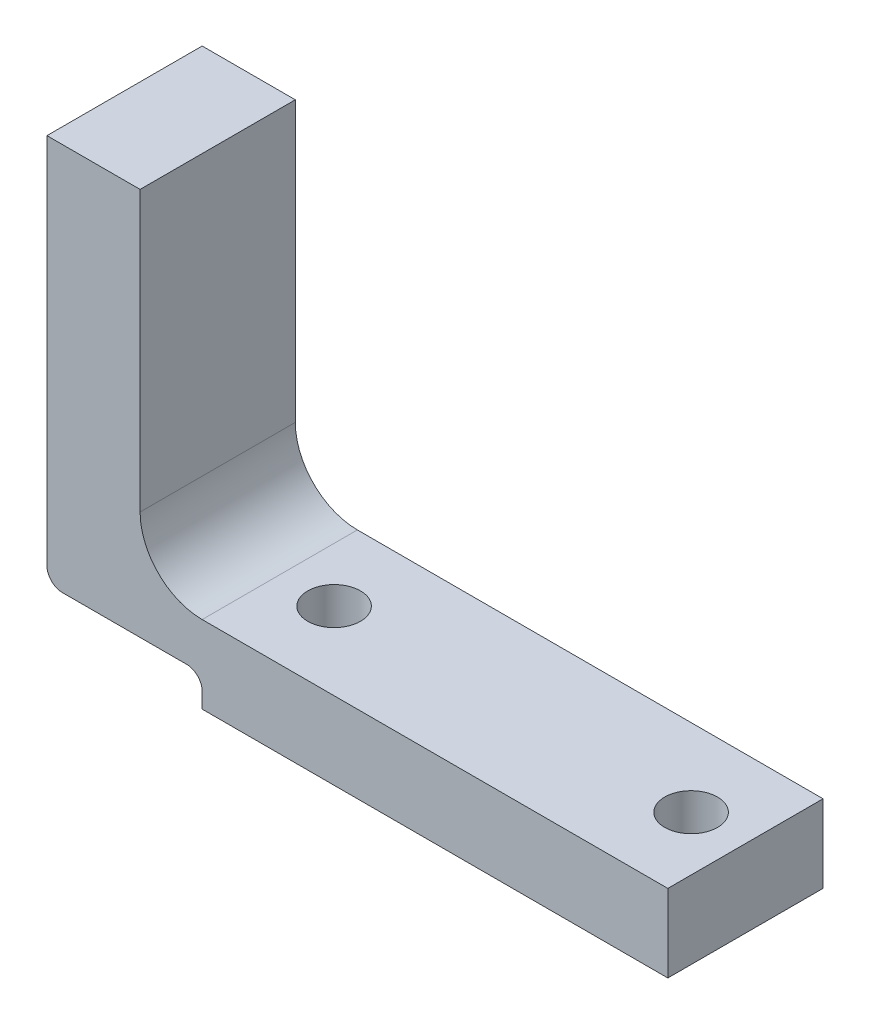
SolidWorks part; units mm, degrees
ref_plane "前视基准面" through (0, 0, 0) normal (0, 0, 1) x (1, 0, 0)
ref_plane "上视基准面" through (0, 0, 0) normal (0, 1, 0) x (1, 0, 0)
ref_plane "右视基准面" through (0, 0, 0) normal (1, 0, 0) x (0, 0, -1)
sketch "草图1" plane through (0, 0, 0) normal (0, 0, 1) x (1, 0, 0)
  line L0 (0, 27) -> (0, 0)
  line L1 (0, 0) -> (40, 0)
  line L2 (40, 0) -> (40, 5)
  line L3 (40, 5) -> (6, 5)
  line L4 (6, 5) -> (6, 27)
  line L5 (6, 27) -> (0, 27)
  dimension "D1" = 34
  dimension "D2" = 27
  dimension "D3" = 6
  dimension "D4" = 5
extrude "凸台-拉伸1" add sketch "草图1" along normal mid plane 10
sketch "草图2" plane through (0, 5, 0) normal (0, 1, 0) x (1, 0, 0)
  line L0 (13.5, 0) -> (36.5, 0)
  dimension "D1" = 23
  dimension "D2" = 3.5
fillet "圆角1" radius 4 1 edges at (6, 5, 0)
hole_wizard "M3 间隙孔1" positions "3D草图1" profile "草图4" hole size "M3" standard "GB" end condition through all
sketch3d "3D草图1"
  point P0 (13.5, 5, 0)
  point P3 (36.5, 5, 0)
sketch "草图4" plane through (13.5, 5, 0) normal (1, 0, 0) x (0, 0, 1)
  line L0 (0, 0) -> (0, 5)
  line L1 (0, 5) -> (1.7, 5)
  line L2 (1.7, 5) -> (1.7, 0)
  line L5 (1.7, 0) -> (0, 0)
  line L11 (0, -6.35) -> (0, 107.95) construction
  dimension "通孔孔直径" = 3.4
  dimension "通孔孔深度" = 5
sketch "草图5" plane through (0, 0, 0) normal (1, 0, 0) x (0, 0, -1)
  line L0 (0, 6) -> (0, 23)
  line L1 (0, 5) -> (0, 27) construction
  line L2 (-5, 27) -> (5, 27) construction
  dimension "D1" = 4
  dimension "D2" = 17
hole_wizard "M3 螺纹孔1" positions "3D草图2" profile "草图6" tap size "M3" standard "GB"
sketch3d "3D草图2"
  point P0 (0, 6, 0)
  point P3 (0, 23, 0)
cosmetic thread "孔螺蚊线1" parameters "D1"=5, "D2"=3
cosmetic thread "孔螺蚊线2" parameters "D1"=5, "D2"=3
sketch "草图6" plane through (0, 6, 0) normal (0, 1, 0) x (0, 0, 1)
  line L0 (0, 0) -> (0, 5.7511)
  line L1 (0, 5.7511) -> (1.25, 5)
  line L2 (1.25, 5) -> (1.25, 0)
  line L5 (1.25, 0) -> (0, 0)
  line L10 (0, 5.7511) -> (-1.25, 5) construction
  line L11 (0, -6.35) -> (0, 107.95) construction
  dimension "螺纹孔钻头直径" = 2.5
  dimension "螺纹孔钻头深度" = 5
  dimension "导头角度" = 118
sketch "草图7" plane through (0, 0, 5) normal (0, 0, 1) x (1, 0, 0)
  line L1 (0, 0) -> (10, 0)
  line L2 (0, 0) -> (0, 2)
  line L3 (0, 2) -> (10, 2)
  line L4 (10, 0) -> (10, 2)
  dimension "D1" = 10
  dimension "D2" = 2
extrude "切除-拉伸1" cut sketch "草图7" against normal through all
fillet "圆角2" radius 1 2 edges at (0, 2, 0) (10, 2, 0)
